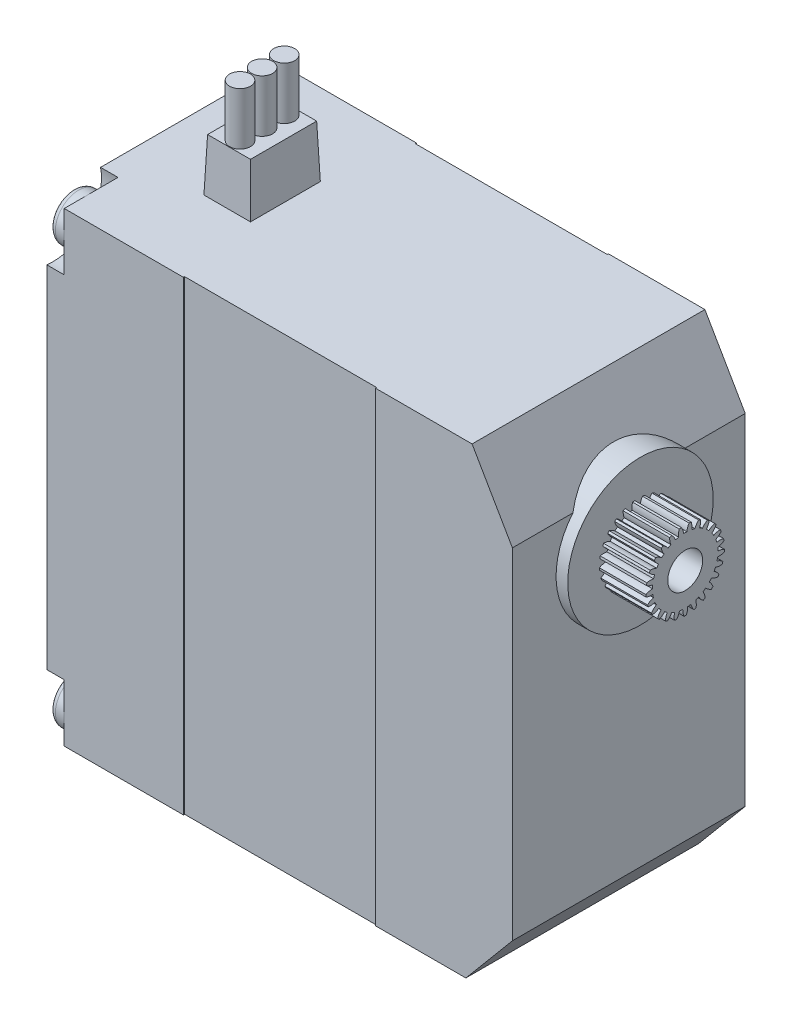
SolidWorks part; units mm, degrees
ref_plane "前视基准面" through (0, 0, 0) normal (0, 0, 1) x (1, 0, 0)
ref_plane "上视基准面" through (0, 0, 0) normal (0, 1, 0) x (1, 0, 0)
ref_plane "右视基准面" through (0, 0, 0) normal (1, 0, 0) x (0, 0, -1)
sketch "草图1" plane through (0, 0, 0) normal (0, 0, 1) x (1, 0, 0)
  line L1 (-20, -20) -> (20, -20)
  line L2 (-20, -20) -> (-20, 20)
  line L3 (-20, 20) -> (20, 20)
  line L4 (20, -20) -> (20, 20)
  line L5 (-20, -20) -> (20, 20) construction
  line L6 (-20, 20) -> (20, -20) construction
  point P0 (0, 0)
  dimension "D1" = 40
  dimension "D2" = 40
extrude "凸台-拉伸1" add sketch "草图1" along normal blind 20
ref_plane "基准面1" through (20, 0, 0) normal (1, 0, 0) x (0, 0, -1)
sketch "草图2" plane through (20, 0, 0) normal (1, 0, 0) x (0, 0, -1)
  line L0 (-10, 20) -> (-10, 10) construction
  line L1 (-20, 20) -> (0, 20) construction
  circle A0 centre (-10, 10) radius 6.25
  dimension "D2" = 12.5
  dimension "D1" = 10
extrude "凸台-拉伸2" add sketch "草图2" along normal blind 1
ref_plane "基准面2" through (-20, 0, 0) normal (-1, 0, 0) x (0, 0, 1)
ref_plane "基准面5" through (20, 0, 0) normal (1, 0, 0) x (0, 0, -1)
ref_plane "基准面8" through (0, 0, 0) normal (0, 0, -1) x (-1, 0, 0)
sketch "草图10" plane through (0, 0, 0) normal (0, 0, -1) x (-1, 0, 0)
  line L0 (-20, 20) -> (20, 20) construction
  line L1 (-8.25, -20) -> (8.25, -20)
  line L2 (-8.25, -20) -> (-8.25, 20)
  line L3 (-8.25, 20) -> (8.25, 20)
  line L4 (8.25, -20) -> (8.25, 20)
  line L5 (-8.25, -20) -> (8.25, 20) construction
  line L6 (-8.25, 20) -> (8.25, -20) construction
  point P0 (0, 0)
  dimension "D1" = 16.5
extrude "切除-拉伸5" cut sketch "草图10" against normal blind 0.1
ref_plane "基准面9" through (0, 0, 20) normal (0, 0, 1) x (1, 0, 0)
sketch "草图11" plane through (0, 0, 20) normal (0, 0, 1) x (1, 0, 0)
  line L0 (20, 20) -> (-20, 20) construction
  line L1 (-8.25, -20) -> (8.25, -20)
  line L2 (-8.25, -20) -> (-8.25, 20)
  line L3 (-8.25, 20) -> (8.25, 20)
  line L4 (8.25, -20) -> (8.25, 20)
  line L5 (-8.25, -20) -> (8.25, 20) construction
  line L6 (-8.25, 20) -> (8.25, -20) construction
  point P0 (0, 0)
  dimension "D1" = 16.5
extrude "切除-拉伸6" cut sketch "草图11" against normal blind 0.1
ref_plane "基准面10" through (0, 20, 0) normal (0, 1, 0) x (1, 0, 0)
ref_plane "基准面11" through (0, -20, 0) normal (0, -1, 0) x (-1, 0, 0)
ref_plane "基准面12" through (21, 0, 0) normal (1, 0, 0) x (0, 0, -1)
sketch "草图14" plane through (21, 0, 0) normal (1, 0, 0) x (0, 0, -1)
  arc A0 (-9.0018, 13.0728) -> (-9.3214, 12.5861) centre (-8.1454, 12.1623) ccw
  arc A1 (-9.3214, 12.5861) -> (-9.5931, 12.6558) centre (-10.1556, 9.9012) ccw
  arc A2 (-9.5931, 12.6558) -> (-9.6387, 13.2363) centre (-10.8278, 12.851) ccw
  arc A3 (-9.6387, 13.2363) -> (-9.8268, 13.2601) centre (-10.1556, 9.9012) ccw
  arc A4 (-9.8268, 13.2601) -> (-10.0153, 12.7092) centre (-8.7709, 12.5912) ccw
  arc A5 (-10.0153, 12.7092) -> (-10.2958, 12.7092) centre (-10.1556, 9.9012) ccw
  arc A6 (-10.2958, 12.7092) -> (-10.4843, 13.2601) centre (-11.5402, 12.5912) ccw
  arc A7 (-10.4843, 13.2601) -> (-10.6725, 13.2363) centre (-10.1556, 9.9012) ccw
  arc A8 (-10.6725, 13.2363) -> (-10.718, 12.6558) centre (-9.4834, 12.851) ccw
  arc A9 (-10.718, 12.6558) -> (-10.9897, 12.5861) centre (-10.1556, 9.9012) ccw
  arc A10 (-10.9897, 12.5861) -> (-11.3093, 13.0728) centre (-12.1657, 12.1623) ccw
  arc A11 (-11.3093, 13.0728) -> (-11.4857, 13.003) centre (-10.1556, 9.9012) ccw
  arc A12 (-11.4857, 13.003) -> (-11.3854, 12.4294) centre (-10.2381, 12.9255) ccw
  arc A13 (-11.3854, 12.4294) -> (-11.6312, 12.2943) centre (-10.1556, 9.9012) ccw
  arc A14 (-11.6312, 12.2943) -> (-12.0618, 12.6863) centre (-12.6649, 11.5913) ccw
  arc A15 (-12.0618, 12.6863) -> (-12.2153, 12.5748) centre (-10.1556, 9.9012) ccw
  arc A16 (-12.2153, 12.5748) -> (-11.9755, 12.0441) centre (-10.9876, 12.81) ccw
  arc A17 (-11.9755, 12.0441) -> (-12.18, 11.8521) centre (-10.1556, 9.9012) ccw
  arc A18 (-12.18, 11.8521) -> (-12.6946, 12.1247) centre (-13.0064, 10.9142) ccw
  arc A19 (-12.6946, 12.1247) -> (-12.8155, 11.9785) centre (-10.1556, 9.9012) ccw
  arc A20 (-12.8155, 11.9785) -> (-12.4513, 11.5242) centre (-11.6848, 12.5117) ccw
  arc A21 (-12.4513, 11.5242) -> (-12.6016, 11.2873) centre (-10.1556, 9.9012) ccw
  arc A22 (-12.6016, 11.2873) -> (-13.1678, 11.4234) centre (-13.1688, 10.1734) ccw
  arc A23 (-13.1678, 11.4234) -> (-13.2485, 11.2518) centre (-10.1556, 9.9012) ccw
  arc A24 (-13.2485, 11.2518) -> (-12.7828, 10.9023) centre (-12.286, 12.0493) ccw
  arc A25 (-12.7828, 10.9023) -> (-12.8695, 10.6355) centre (-10.1556, 9.9012) ccw
  arc A26 (-12.8695, 10.6355) -> (-13.4517, 10.6265) centre (-13.1418, 9.4155) ccw
  arc A27 (-13.4517, 10.6265) -> (-13.4872, 10.4402) centre (-10.1556, 9.9012) ccw
  arc A28 (-13.4872, 10.4402) -> (-12.9492, 10.2175) centre (-12.7533, 11.452) ccw
  arc A29 (-12.9492, 10.2175) -> (-12.9668, 9.9375) centre (-10.1556, 9.9012) ccw
  arc A30 (-12.9668, 9.9375) -> (-13.5285, 9.784) centre (-12.9272, 8.6881) ccw
  arc A31 (-13.5285, 9.784) -> (-13.5166, 9.5947) centre (-10.1556, 9.9012) ccw
  arc A32 (-13.5166, 9.5947) -> (-12.9401, 9.5128) centre (-13.0574, 10.7573) ccw
  arc A33 (-12.9401, 9.5128) -> (-12.8875, 9.2372) centre (-10.1556, 9.9012) ccw
  arc A34 (-12.8875, 9.2372) -> (-13.3934, 8.9488) centre (-12.5384, 8.0369) ccw
  arc A35 (-13.3934, 8.9488) -> (-13.3348, 8.7685) centre (-10.1556, 9.9012) ccw
  arc A36 (-13.3348, 8.7685) -> (-12.756, 8.8325) centre (-13.1791, 10.0087) ccw
  arc A37 (-12.756, 8.8325) -> (-12.6366, 8.5787) centre (-10.1556, 9.9012) ccw
  arc A38 (-12.6366, 8.5787) -> (-13.0549, 8.1735) centre (-12, 7.5029) ccw
  arc A39 (-13.0549, 8.1735) -> (-12.9532, 8.0134) centre (-10.1556, 9.9012) ccw
  arc A40 (-12.9532, 8.0134) -> (-12.4086, 8.2194) centre (-13.1109, 9.2534) ccw
  arc A41 (-12.4086, 8.2194) -> (-12.2298, 8.0032) centre (-10.1556, 9.9012) ccw
  arc A42 (-12.2298, 8.0032) -> (-12.5341, 7.5068) centre (-11.3456, 7.1196) ccw
  arc A43 (-12.5341, 7.5068) -> (-12.3959, 7.3769) centre (-10.1556, 9.9012) ccw
  arc A44 (-12.3959, 7.3769) -> (-11.9195, 7.7119) centre (-12.8569, 8.5388) ccw
  arc A45 (-11.9195, 7.7119) -> (-11.6926, 7.547) centre (-10.1556, 9.9012) ccw
  arc A46 (-11.6926, 7.547) -> (-11.8639, 6.9905) centre (-10.6165, 6.911) ccw
  arc A47 (-11.8639, 6.9905) -> (-11.6977, 6.8991) centre (-10.1556, 9.9012) ccw
  arc A48 (-11.6977, 6.8991) -> (-11.3197, 7.342) centre (-12.4333, 7.9098) ccw
  arc A49 (-11.3197, 7.342) -> (-11.0588, 7.2387) centre (-10.1556, 9.9012) ccw
  arc A50 (-11.0588, 7.2387) -> (-11.0864, 6.6571) centre (-9.8584, 6.8903) ccw
  arc A51 (-11.0864, 6.6571) -> (-10.9027, 6.6099) centre (-10.1556, 9.9012) ccw
  arc A52 (-10.9027, 6.6099) -> (-10.6467, 7.1329) centre (-11.8665, 7.4059) ccw
  arc A53 (-10.6467, 7.1329) -> (-10.3683, 7.0977) centre (-10.1556, 9.9012) ccw
  arc A54 (-10.3683, 7.0977) -> (-10.2504, 6.5275) centre (-9.1189, 7.0588) ccw
  arc A55 (-10.2504, 6.5275) -> (-10.0607, 6.5275) centre (-10.1556, 9.9012) ccw
  arc A56 (-10.0607, 6.5275) -> (-9.9428, 7.0977) centre (-11.1922, 7.0588) ccw
  arc A57 (-9.9428, 7.0977) -> (-9.6645, 7.1329) centre (-10.1556, 9.9012) ccw
  arc A58 (-9.6645, 7.1329) -> (-9.4084, 6.6099) centre (-8.4447, 7.4059) ccw
  arc A59 (-9.4084, 6.6099) -> (-9.2247, 6.6571) centre (-10.1556, 9.9012) ccw
  arc A60 (-9.2247, 6.6571) -> (-9.2523, 7.2387) centre (-10.4528, 6.8903) ccw
  arc A61 (-9.2523, 7.2387) -> (-8.9915, 7.342) centre (-10.1556, 9.9012) ccw
  arc A62 (-8.9915, 7.342) -> (-8.6134, 6.8991) centre (-7.8779, 7.9098) ccw
  arc A63 (-8.6134, 6.8991) -> (-8.4472, 6.9905) centre (-10.1556, 9.9012) ccw
  arc A64 (-8.4472, 6.9905) -> (-8.6185, 7.547) centre (-9.6947, 6.911) ccw
  arc A65 (-8.6185, 7.547) -> (-8.3916, 7.7119) centre (-10.1556, 9.9012) ccw
  arc A66 (-8.3916, 7.7119) -> (-7.9153, 7.3769) centre (-7.4542, 8.5388) ccw
  arc A67 (-7.9153, 7.3769) -> (-7.777, 7.5068) centre (-10.1556, 9.9012) ccw
  arc A68 (-7.777, 7.5068) -> (-8.0814, 8.0032) centre (-8.9655, 7.1196) ccw
  arc A69 (-8.0814, 8.0032) -> (-7.9026, 8.2194) centre (-10.1556, 9.9012) ccw
  arc A70 (-7.9026, 8.2194) -> (-7.3579, 8.0134) centre (-7.2003, 9.2534) ccw
  arc A71 (-7.3579, 8.0134) -> (-7.2563, 8.1735) centre (-10.1556, 9.9012) ccw
  arc A72 (-7.2563, 8.1735) -> (-7.6745, 8.5787) centre (-8.3112, 7.5029) ccw
  arc A73 (-7.6745, 8.5787) -> (-7.5551, 8.8325) centre (-10.1556, 9.9012) ccw
  arc A74 (-7.5551, 8.8325) -> (-6.9763, 8.7685) centre (-7.132, 10.0087) ccw
  arc A75 (-6.9763, 8.7685) -> (-6.9177, 8.9488) centre (-10.1556, 9.9012) ccw
  arc A76 (-6.9177, 8.9488) -> (-7.4236, 9.2372) centre (-7.7727, 8.0369) ccw
  arc A77 (-7.4236, 9.2372) -> (-7.371, 9.5128) centre (-10.1556, 9.9012) ccw
  arc A78 (-7.371, 9.5128) -> (-6.7945, 9.5947) centre (-7.2538, 10.7573) ccw
  arc A79 (-6.7945, 9.5947) -> (-6.7826, 9.784) centre (-10.1556, 9.9012) ccw
  arc A80 (-6.7826, 9.784) -> (-7.3443, 9.9375) centre (-7.3839, 8.6881) ccw
  arc A81 (-7.3443, 9.9375) -> (-7.3619, 10.2175) centre (-10.1556, 9.9012) ccw
  arc A82 (-7.3619, 10.2175) -> (-6.8239, 10.4402) centre (-7.5578, 11.452) ccw
  arc A83 (-6.8239, 10.4402) -> (-6.8594, 10.6265) centre (-10.1556, 9.9012) ccw
  arc A84 (-6.8594, 10.6265) -> (-7.4417, 10.6355) centre (-7.1693, 9.4155) ccw
  arc A85 (-7.4417, 10.6355) -> (-7.5283, 10.9023) centre (-10.1556, 9.9012) ccw
  arc A86 (-7.5283, 10.9023) -> (-7.0626, 11.2518) centre (-8.0251, 12.0493) ccw
  arc A87 (-7.0626, 11.2518) -> (-7.1434, 11.4234) centre (-10.1556, 9.9012) ccw
  arc A88 (-7.1434, 11.4234) -> (-7.7095, 11.2873) centre (-7.1424, 10.1734) ccw
  arc A89 (-7.7095, 11.2873) -> (-7.8599, 11.5242) centre (-10.1556, 9.9012) ccw
  arc A90 (-7.8599, 11.5242) -> (-7.4957, 11.9785) centre (-8.6263, 12.5117) ccw
  arc A91 (-7.4957, 11.9785) -> (-7.6166, 12.1247) centre (-10.1556, 9.9012) ccw
  arc A92 (-7.6166, 12.1247) -> (-8.1311, 11.8521) centre (-7.3047, 10.9142) ccw
  arc A93 (-8.1311, 11.8521) -> (-8.3356, 12.0441) centre (-10.1556, 9.9012) ccw
  arc A94 (-8.3356, 12.0441) -> (-8.0959, 12.5748) centre (-9.3235, 12.81) ccw
  arc A95 (-8.0959, 12.5748) -> (-8.2493, 12.6863) centre (-10.1556, 9.9012) ccw
  arc A96 (-8.2493, 12.6863) -> (-8.6799, 12.2943) centre (-7.6462, 11.5913) ccw
  arc A97 (-8.6799, 12.2943) -> (-8.9257, 12.4294) centre (-10.1556, 9.9012) ccw
  arc A98 (-8.9257, 12.4294) -> (-8.8255, 13.003) centre (-10.0731, 12.9255) ccw
  arc A99 (-8.8255, 13.003) -> (-9.0018, 13.0728) centre (-10.1556, 9.9012) ccw
extrude "凸台-拉伸6" add sketch "草图14" along normal blind 4
ref_plane "基准面13" through (25, 0, 0) normal (1, 0, 0) x (0, 0, -1)
sketch "草图15" plane through (25, 0, 0) normal (1, 0, 0) x (0, 0, -1)
  circle A0 centre (-10.1556, 9.9012) radius 1.5
extrude "切除-拉伸9" cut sketch "草图15" against normal blind 4
ref_plane "基准面14" through (0, 20, 0) normal (0, 1, 0) x (1, 0, 0)
ref_plane "基准面15" through (-20, 0, 0) normal (-1, 0, 0) x (0, 0, 1)
chamfer "倒角2" distance 6 angle 30 1 edges at (20, 20, 10) first distance on face at (20, 0, 10)
chamfer "倒角3" distance 4 angle 50 1 edges at (20, -20, 10) first distance on face at (0, -20, 10)
ref_plane "基准面18" through (0, -20, 0) normal (0, -1, 0) x (-1, 0, 0)
sketch "草图20" plane through (0, -20, 0) normal (0, -1, 0) x (-1, 0, 0)
  line L0 (-20, 1.0461) -> (-20, -15.8444) construction
  line L2 (-20, 0) -> (-7, 0) construction
  line L3 (6.4625, 0) -> (-6.4625, 0) construction
  line L4 (-7, 0) -> (-7, -0.8546) construction
  line L7 (-5.9416, -19.9) -> (-4.5261, -19.9) construction
  line L9 (-6.0182, -0.1) -> (-4.3371, -0.1) construction
  line L10 (-7, -0.1) -> (-7, -19.9) construction
  line L11 (-7, -19.9) -> (-10, -19.9) construction
  line L12 (-10, -19.9) -> (-10, 0) construction
  line L13 (-10, 0) -> (-7, 0) construction
  line L14 (-10, -0.1) -> (-7, -0.1)
  line L15 (-7, -0.1) -> (-7, -19.9)
  line L16 (-7, -19.9) -> (-10, -19.9)
  line L17 (-10, -19.9) -> (-10, -0.1)
sketch "草图24" plane through (-20, 0, 0) normal (-1, 0, 0) x (0, 0, 1)
  line L0 (20, 0) -> (0, 0) construction
  line L1 (20, -6.4625) -> (20, 6.4625) construction
  line L2 (10, 0) -> (10, 28.881) construction
  line L3 (0, 6.4625) -> (0, -6.4625) construction
  line L4 (11, 20) -> (-11, 20) construction
  line L5 (0, 15.0598) -> (0, 20)
  line L6 (0, 20) -> (4.6197, 20)
  line L7 (20, 15.0598) -> (20, 20)
  line L8 (20, 20) -> (15.3803, 20)
  line L9 (0, -20) -> (4.6197, -20)
  line L10 (0, -15.0598) -> (0, -20)
  line L11 (20, -20) -> (15.3803, -20)
  line L12 (20, -15.0598) -> (20, -20)
  arc A1 (4.6197, 20) -> (0, 15.0598) centre (0.55, 19.1756) cw
  arc A2 (15.3803, 20) -> (20, 15.0598) centre (19.45, 19.1756) ccw
  arc A3 (4.6197, -20) -> (0, -15.0598) centre (0.55, -19.1756) ccw
  arc A5 (15.3803, -20) -> (20, -15.0598) centre (19.45, -19.1756) cw
extrude "切除-拉伸13" cut sketch "草图24" against normal blind 1.5
ref_plane "基准面20" through (-18.5, 0, 0) normal (-1, 0, 0) x (0, 0, 1)
sketch "草图25" plane through (-18.5, 0, 0) normal (-1, 0, 0) x (0, 0, 1)
  line L0 (0, 0) -> (20, 0) construction
  line L1 (20, -6.4625) -> (20, 6.4625) construction
  line L2 (10, 0) -> (10, 8.1993) construction
  circle A0 centre (2.0399, 17.9472) radius 2
  circle A1 centre (17.9601, 17.9472) radius 2
  circle A2 centre (2.0399, -17.9472) radius 2
  circle A3 centre (17.9601, -17.9472) radius 2
extrude "凸台-拉伸10" add sketch "草图25" along normal blind 1.3
fillet "圆角5" radius 0.5 4 edges at (-19.8, -17.9472, 19.9601) (-19.8, -17.9472, 0.0399) (-19.8, 17.9472, 15.9601) (-19.8, 17.9472, 4.0399)
ref_plane "基准面21" through (-19.8, 0, 0) normal (-1, 0, 0) x (0, 0, 1)
sketch "草图26" plane through (-19.8, 0, 0) normal (-1, 0, 0) x (0, 0, 1)
  line L0 (1.6399, 18.3472) -> (0.5942, 18.3472)
  line L1 (1.6399, 16.5015) -> (2.4399, 16.5015)
  line L2 (1.6399, 16.5015) -> (1.6399, 17.5472)
  line L3 (1.6399, 19.3929) -> (2.4399, 19.3929)
  line L4 (2.4399, 16.5015) -> (2.4399, 17.5472)
  line L5 (1.6399, 16.5015) -> (2.4399, 19.3929) construction
  line L6 (1.6399, 19.3929) -> (2.4399, 16.5015) construction
  line L7 (3.4855, 17.5472) -> (2.4399, 17.5472)
  line L8 (3.4855, 17.5472) -> (3.4855, 18.3472)
  line L9 (3.4855, 18.3472) -> (2.4399, 18.3472)
  line L10 (0.5942, 17.5472) -> (0.5942, 18.3472)
  line L11 (3.4855, 17.5472) -> (0.5942, 18.3472) construction
  line L12 (3.4855, 18.3472) -> (0.5942, 17.5472) construction
  line L13 (2.4399, 18.3472) -> (2.4399, 19.3929)
  line L14 (1.6399, 17.5472) -> (0.5942, 17.5472)
  line L15 (1.6399, 18.3472) -> (1.6399, 19.3929)
  line L16 (0, 0) -> (20.0276, 0) construction
  line L17 (10.0138, 0) -> (10.0138, 3.4562) construction
  line L18 (16.542, 18.3472) -> (19.4334, 17.5472) construction
  line L19 (16.542, 17.5472) -> (19.4334, 18.3472) construction
  line L20 (18.3877, 19.3929) -> (17.5877, 16.5015) construction
  line L21 (18.3877, 16.5015) -> (17.5877, 19.3929) construction
  line L22 (18.3877, 18.3472) -> (18.3877, 19.3929)
  line L23 (18.3877, 17.5472) -> (19.4334, 17.5472)
  line L24 (17.5877, 18.3472) -> (17.5877, 19.3929)
  line L25 (19.4334, 17.5472) -> (19.4334, 18.3472)
  line L26 (16.542, 18.3472) -> (17.5877, 18.3472)
  line L27 (16.542, 17.5472) -> (16.542, 18.3472)
  line L28 (16.542, 17.5472) -> (17.5877, 17.5472)
  line L29 (17.5877, 16.5015) -> (17.5877, 17.5472)
  line L30 (18.3877, 19.3929) -> (17.5877, 19.3929)
  line L31 (18.3877, 16.5015) -> (18.3877, 17.5472)
  line L32 (18.3877, 16.5015) -> (17.5877, 16.5015)
  line L33 (18.3877, 18.3472) -> (19.4334, 18.3472)
  line L34 (18.3877, -16.5015) -> (17.5877, -19.3929) construction
  line L35 (18.3877, -19.3929) -> (17.5877, -16.5015) construction
  line L36 (16.542, -17.5472) -> (19.4334, -18.3472) construction
  line L37 (16.542, -18.3472) -> (19.4334, -17.5472) construction
  line L38 (3.4855, -18.3472) -> (0.5942, -17.5472) construction
  line L39 (3.4855, -17.5472) -> (0.5942, -18.3472) construction
  line L40 (1.6399, -19.3929) -> (2.4399, -16.5015) construction
  line L41 (1.6399, -16.5015) -> (2.4399, -19.3929) construction
  line L42 (18.3877, -18.3472) -> (19.4334, -18.3472)
  line L43 (18.3877, -16.5015) -> (17.5877, -16.5015)
  line L44 (18.3877, -16.5015) -> (18.3877, -17.5472)
  line L45 (18.3877, -19.3929) -> (17.5877, -19.3929)
  line L46 (17.5877, -16.5015) -> (17.5877, -17.5472)
  line L47 (16.542, -17.5472) -> (17.5877, -17.5472)
  line L48 (16.542, -17.5472) -> (16.542, -18.3472)
  line L49 (16.542, -18.3472) -> (17.5877, -18.3472)
  line L50 (19.4334, -17.5472) -> (19.4334, -18.3472)
  line L51 (17.5877, -18.3472) -> (17.5877, -19.3929)
  line L52 (18.3877, -17.5472) -> (19.4334, -17.5472)
  line L53 (18.3877, -18.3472) -> (18.3877, -19.3929)
  line L54 (1.6399, -18.3472) -> (1.6399, -19.3929)
  line L55 (1.6399, -17.5472) -> (0.5942, -17.5472)
  line L56 (2.4399, -18.3472) -> (2.4399, -19.3929)
  line L57 (0.5942, -17.5472) -> (0.5942, -18.3472)
  line L58 (3.4855, -18.3472) -> (2.4399, -18.3472)
  line L59 (3.4855, -17.5472) -> (3.4855, -18.3472)
  line L60 (3.4855, -17.5472) -> (2.4399, -17.5472)
  line L61 (2.4399, -16.5015) -> (2.4399, -17.5472)
  line L62 (1.6399, -19.3929) -> (2.4399, -19.3929)
  line L63 (1.6399, -16.5015) -> (1.6399, -17.5472)
  line L64 (1.6399, -16.5015) -> (2.4399, -16.5015)
  line L65 (1.6399, -18.3472) -> (0.5942, -18.3472)
  circle A0 centre (2.0399, 17.9472) radius 1.5 construction
  point P0 (2.0399, 17.9472)
  point P8 (2.0399, 17.9472)
  point P34 (17.9877, 17.9472)
  point P59 (17.9877, -17.9472)
  point P60 (2.0399, -17.9472)
extrude "切除-拉伸14" cut sketch "草图26" against normal blind 0.8 draft 16
ref_plane "基准面22" through (0, 20, 0) normal (0, 1, 0) x (1, 0, 0)
sketch "草图28" plane through (0, 20, 0) normal (0, 1, 0) x (1, 0, 0)
  line L0 (-20, 0) -> (-20, -20) construction
  line L1 (-20, 11) -> (-20, -11) construction
  line L2 (-6.4625, -20) -> (6.4625, -20) construction
  line L3 (-20, -10) -> (-10.9126, -10) construction
  line L4 (-20, -10) -> (-9.5, -10) construction
  line L5 (-9.5, -10) -> (-9.5, -7)
  line L6 (-9.5, -7) -> (-13.5, -7)
  line L7 (-13.5, -7) -> (-13.5, -13)
  line L8 (-13.5, -13) -> (-9.5, -13)
  line L9 (-9.5, -13) -> (-9.5, -10)
extrude "凸台-拉伸11" add sketch "草图28" along normal blind 4.5 draft 2
ref_plane "基准面23" through (0, 24.5, 0) normal (0, 1, 0) x (1, 0, 0)
sketch "草图29" plane through (0, 24.5, 0) normal (0, 1, 0) x (1, 0, 0)
  line L0 (-11.5, -7.1571) -> (-11.5, -14.7571) construction
  line L1 (-9.6571, -7.1571) -> (-13.3429, -7.1571) construction
  line L2 (-11.5, -10.9571) -> (-11.5, -7.1571) construction
  line L3 (-11.5, -10.9571) -> (-11.5, -12.8429) construction
  line L4 (-13.3429, -12.8429) -> (-9.6571, -12.8429) construction
  circle A0 centre (-11.5, -11.9) radius 0.9
  circle A1 centre (-11.5, -8.1) radius 0.9
  circle A2 centre (-11.5, -10.0025) radius 0.9
extrude "凸台-拉伸12" add sketch "草图29" along normal blind 4.5
